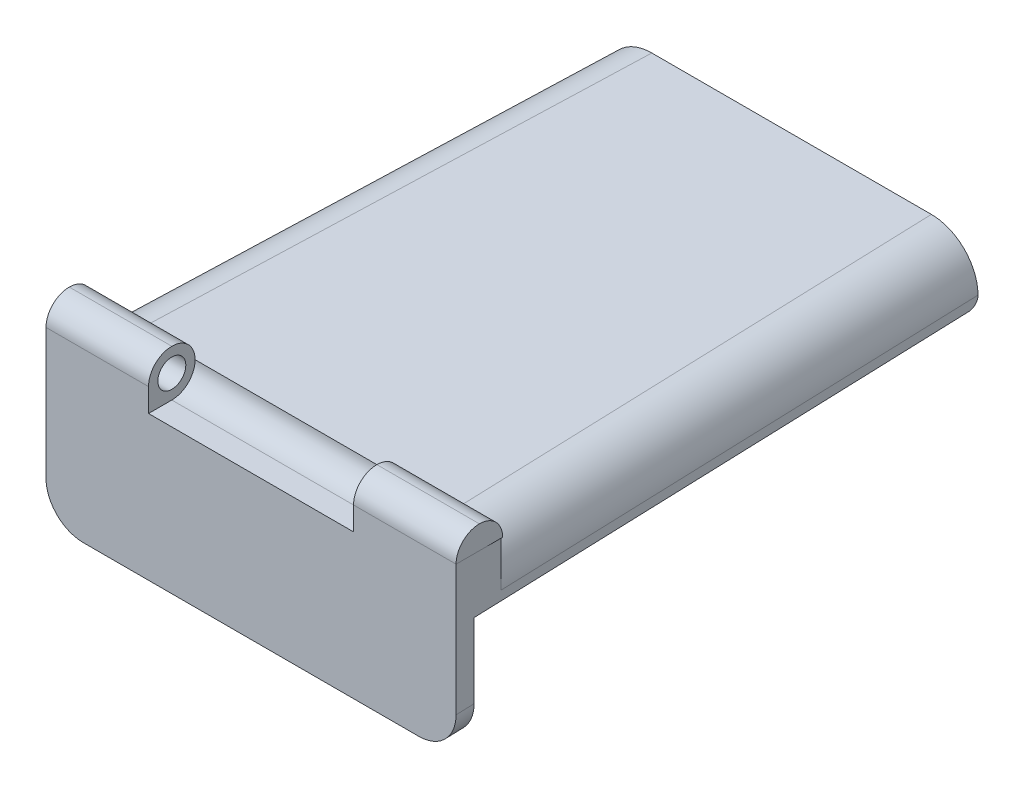
SolidWorks part; units mm, degrees
material "PF"
ref_plane "Спереди" through (0, 0, 0) normal (0, 0, 1) x (1, 0, 0)
ref_plane "Сверху" through (0, 0, 0) normal (0, 1, 0) x (1, 0, 0)
ref_plane "Справа" through (0, 0, 0) normal (1, 0, 0) x (0, 0, -1)
sketch "Эскиз1" plane through (0, 0, 0) normal (1, 0, 0) x (0, 0, -1)
  line L0 (-9.0774, 0) -> (61.2488, 0) construction
  line L1 (0, -21.7381) -> (0, 22.2158) construction
  line L2 (0, -18) -> (0, 0)
  line L3 (0, 0) -> (58, 0)
  line L4 (58, 0) -> (58, -6)
  line L5 (58, -6) -> (2, -6)
  line L6 (2, -6) -> (2, -18)
  line L7 (2, -18) -> (0, -18)
  dimension "D1" = 58
  dimension "D2" = 6
  dimension "D3" = 12
  dimension "D4" = 2
extrude "Бобышка-Вытянуть1" add sketch "Эскиз1" along normal mid plane 44
sketch "Эскиз2" plane through (0, 0, 0) normal (1, 0, 0) x (0, 0, -1)
  line L0 (-4.3435, 0) -> (61.7743, 0) construction
  line L1 (2, -6) -> (48, -6)
  line L2 (2, -6) -> (58, -6) construction
  line L3 (48, -6) -> (48, -7)
  line L4 (48, -7) -> (3, -7)
  line L5 (3, -7) -> (3, -17)
  line L6 (3, -17) -> (2, -17)
  line L7 (2, -18) -> (2, -6) construction
  line L8 (2, -17) -> (2, -6)
  line L9 (0, -18) -> (2, -18) construction
  line L10 (58, -6) -> (58, 0) construction
  dimension "D1" = 1
  dimension "D2" = 1
  dimension "D3" = 1
  dimension "D4" = 10
extrude "Бобышка-Вытянуть2" add sketch "Эскиз2" along normal mid plane 42
sketch "Эскиз3" plane through (0, 0, 0) normal (0, 1, 0) x (1, 0, 0)
  line L0 (0, -2.2315) -> (0, 58.9159) construction
  line L1 (-20, 58) -> (-22, 58)
  line L2 (22, 58) -> (-22, 58) construction
  line L3 (-22, 58) -> (-22, 0)
  line L4 (-22, 0) -> (-20, 58)
  line L5 (22, 58) -> (22, 0)
  line L6 (22, 0) -> (20, 58)
  line L7 (20, 58) -> (22, 58)
  dimension "D1" = 20
extrude "Вырез-Вытянуть1" cut sketch "Эскиз3" against normal up to surface (18 mm away) up to face at (0, -18, -1)
sketch "Эскиз4" plane through (0, -6, 0) normal (0, -1, 0) x (1, 0, 0)
  line L0 (0, 2.4946) -> (0, -60.3367) construction
  line L1 (-20.9304, -2) -> (-19.3442, -48)
  line L2 (21.931, -2) -> (-21.931, -2) construction
  line L3 (20.3448, -48) -> (-20.3448, -48) construction
  line L4 (-19.3442, -48) -> (-20.3448, -48)
  line L5 (-20.3448, -48) -> (-21.931, -2)
  line L6 (-21.931, -2) -> (-20.9304, -2)
  line L7 (19.3442, -48) -> (20.3448, -48)
  line L8 (20.9304, -2) -> (19.3442, -48)
  line L9 (20.3448, -48) -> (21.931, -2)
  line L10 (21.931, -2) -> (20.9304, -2)
  dimension "D1" = 1
extrude "Вырез-Вытянуть2" cut sketch "Эскиз4" along normal up to surface (11 mm away) up to face at (0, -17, -2.5)
fillet "Скругление2" radius 3 4 edges at (-20.9132, -17, -2.5) (20.9132, -17, -2.5) (-19.3442, -6.5, -48) (19.3442, -6.5, -48)
fillet "Скругление3" radius 4 2 edges at (-21.9655, -18, -1) (21.9655, -18, -1)
sketch "Эскиз6" plane through (0, 0, 0) normal (0, 0, 1) x (1, 0, 0)
  line L0 (0, 4.3108) -> (0, -21.1694) construction
  line L1 (-22, 0) -> (-11, 0)
  line L2 (22, 0) -> (11, 0)
  line L3 (22, 0) -> (22, 2.5)
  line L4 (22, 2.5) -> (11, 2.5)
  line L5 (11, 0) -> (11, 2.5)
  line L6 (-22, 0) -> (-22, 2.5)
  line L7 (-11, 0) -> (-11, 2.5)
  line L8 (-22, 2.5) -> (-11, 2.5)
  dimension "D1" = 11
  dimension "D2" = 2.5
extrude "Бобышка-Вытянуть6" add sketch "Эскиз6" against normal blind 5
fillet "Скругление4" radius 5 2 edges at (20.9138, 0, -31.5) (-20.9138, 0, -31.5)
fillet "Скругление5" radius 2.5 4 edges at (-16.5, 2.5, -5) (-16.5, 2.5, 0) (16.5, 2.5, -5) (16.5, 2.5, 0)
sketch "Эскиз7" plane through (0, 0, 0) normal (1, 0, 0) x (0, 0, -1)
  line L0 (-1.9038, 0) -> (60.3104, 0) construction
  line L1 (2.5, 2.5) -> (2.5, -7.927) construction
  circle A0 centre (2.5, 0) radius 1.5
  dimension "D1" = 3
extrude "Вырез-Вытянуть3" cut sketch "Эскиз7" against normal mid plane 32
sketch "Эскиз8" plane through (0, 0, 0) normal (1, 0, 0) x (0, 0, -1)
  line L0 (-2.839, 0) -> (12.2062, 0) construction
  line L1 (2.5, 2.5) -> (2.5, -10.4134) construction
  line L2 (2.5, -2.5) -> (0, -2.5)
  line L3 (0, 0) -> (0, -14) construction
  line L4 (0, -2.5) -> (0, 0)
  arc A0 (2.5, -2.5) -> (0, 0) centre (2.5, 0) ccw
  dimension "D1" = 5
extrude "Вырез-Вытянуть4" cut sketch "Эскиз8" against normal mid plane 22
sketch "Эскиз9" plane through (0, 0, -58) normal (0, 0, -1) x (-1, 0, 0)
  line L0 (0, 3.5248) -> (0, -8.2281) construction
  line L3 (-14.997, -1) -> (14.997, -1)
  line L4 (-14.997, -1) -> (14.997, -1)
  line L6 (19, -6) -> (19, -5)
  line L7 (-19, -6) -> (-19, -5)
  line L8 (-19, -6) -> (-19, -5)
  line L9 (-19, -6) -> (19, -6)
  spline S0 degree 3 poles (-2796.9206, -1109.4387) (96.8839, -159.1069) (4.1053, 7.2374) (-17.0132, -1.505) (-17.4573, -1.8015) (-18.1983, -2.5421) (-18.4949, -2.9858) (-27.2466, -24.1017) (139.4549, -116.8108) (1089.1103, 2776.9823) knots -10.405143 -10.405143 -10.405143 -10.405143 0.25 0.25 0.5 0.5 0.75 0.75 11.413727 11.413727 11.413727 11.413727 only from (-14.997, -1) to (-19, -5)
  spline S1 degree 3 poles (-14.997, -1) (-15.5211, -1) (-16.045, -1.1041) (-17.0132, -1.505) (-17.4573, -1.8015) (-18.1983, -2.5421) (-18.4949, -2.9858) (-18.8958, -3.9532) (-19, -4.4765) (-19, -5) knots 0 0 0 0 0.25 0.25 0.5 0.5 0.75 0.75 1 1 1 1
  spline S2 degree 3 poles (14.997, -1) (15.5211, -1) (16.045, -1.1041) (17.0132, -1.505) (17.4573, -1.8015) (18.1983, -2.5421) (18.4949, -2.9858) (18.8958, -3.9532) (19, -4.4765) (19, -5) knots 0 0 0 0 0.25 0.25 0.5 0.5 0.75 0.75 1 1 1 1
  dimension "D1" = 1
  dimension "D2" = 1
  dimension "D3" = 1
extrude "Вырез-Вытянуть5" cut sketch "Эскиз9" against normal blind 0.5
fillet "Скругление7" radius 1.5 1 edges at (0, -6, -57.5)
fillet "Скругление8" radius 1 2 edges at (-19.5, -6, -58) (19.5, -6, -58)
sketch "Эскиз10" plane through (0, 0, 0) normal (1, 0, 0) x (0, 0, -1)
  line L0 (-3.0022, 0) -> (64.9165, 0) construction
  line L1 (58, 3.3325) -> (58, -15.3756) construction
  line L3 (58, -5) -> (58, 0) construction
  line L4 (37.2203, -7) -> (65.8112, -7) construction
  line L5 (3, -7) -> (45.1034, -7) construction
  circle A0 centre (58, -7) radius 4.5
  dimension "D1" = 9
extrude "Бобышка-Вытянуть7" add sketch "Эскиз10" along normal mid plane 16
sketch "Эскиз11" plane through (8, 0, 0) normal (1, 0, 0) x (0, 0, -1)
  circle A0 centre (58, -7) radius 1.5
  dimension "D1" = 3
extrude "Вырез-Вытянуть6" cut sketch "Эскиз11" against normal blind 3
sketch "Эскиз12" plane through (-8, 0, 0) normal (-1, 0, 0) x (0, 0, 1)
  circle A2 centre (-58, -7) radius 1.5
  circle A3 centre (-58, -7) radius 1.5
  dimension "D1" = 0
extrude "Вырез-Вытянуть7" cut sketch "Эскиз12" against normal blind 3
ref_axis "Ось1" through (8, -7, -58) along (-1, 0, 0)
ref_plane "Плоскость1" through (0, -7, 0) normal (0, 1, 0) x (-1, 0, 0)
sketch "Эскиз13" plane through (0, -7, 0) normal (0, 1, 0) x (-1, 0, 0)
  line L0 (0, -64.6778) -> (0, 2.8015) construction
  line L1 (-21.0944, -58) -> (24.2132, -58) construction
  line L2 (-8, -62.5) -> (8, -62.5) construction
  line L3 (-14.5, -58) -> (-8, -58)
  line L4 (-8, -58) -> (-8, -62.5)
  line L6 (-8, -62.5) -> (-10, -62.5)
  line L7 (8, -58) -> (8, -62.5)
  line L8 (8, -62.5) -> (10, -62.5)
  line L9 (14.5, -58) -> (8, -58)
  arc A0 (-10, -62.5) -> (-14.5, -58) centre (-10, -58) cw
  arc A1 (10, -62.5) -> (14.5, -58) centre (10, -58) ccw
  dimension "D1" = 4.5
  dimension "D2" = 2
revolve "Вырез-Повернуть1" cut sketch "Эскиз13" angle 360 about L1
